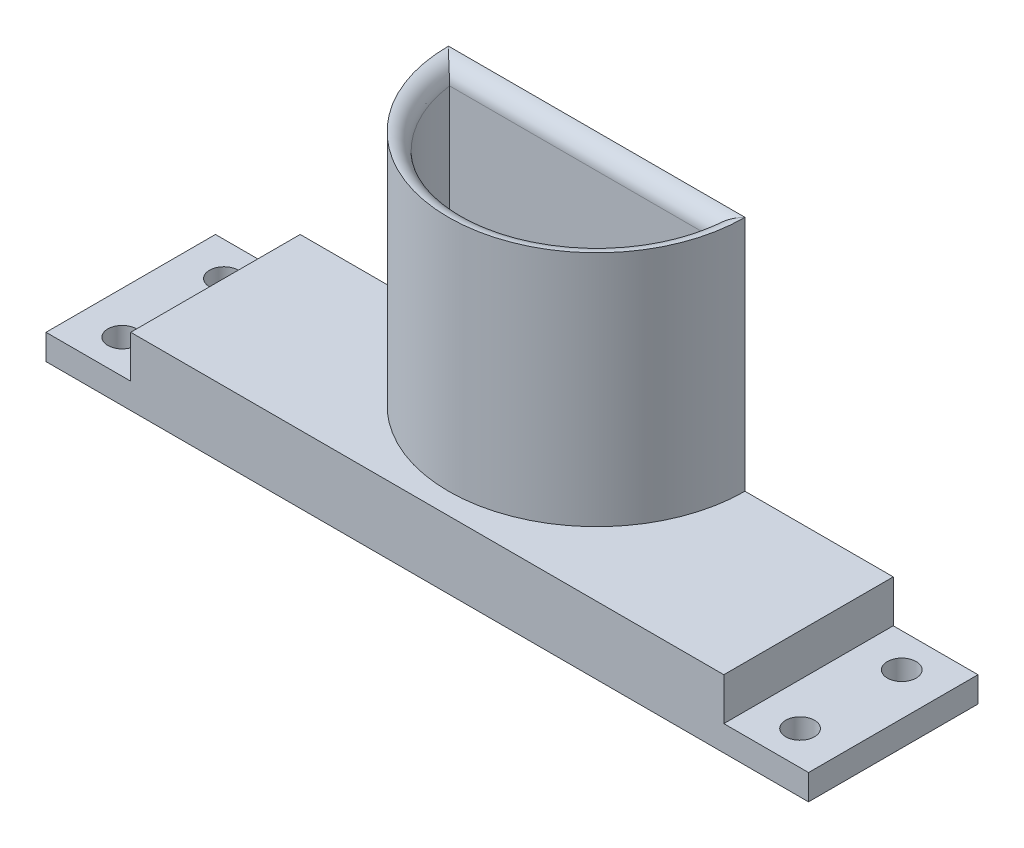
SolidWorks part; units mm, degrees
ref_plane "Front Plane" through (0, 0, 0) normal (0, 0, 1) x (1, 0, 0)
ref_plane "Top Plane" through (0, 0, 0) normal (0, 1, 0) x (1, 0, 0)
ref_plane "Right Plane" through (0, 0, 0) normal (1, 0, 0) x (0, 0, -1)
sketch "Sketch1" plane through (0, 0, 0) normal (0, 1, 0) x (1, 0, 0)
  line L1 (-35, -10) -> (35, -10)
  line L2 (-35, -10) -> (-35, 10)
  line L3 (-35, 10) -> (35, 10)
  line L4 (35, -10) -> (35, 10)
  line L5 (-35, -10) -> (35, 10) construction
  line L6 (-35, 10) -> (35, -10) construction
  point P0 (0, 0)
  dimension "D1" = 70
  dimension "D2" = 20
extrude "Boss-Extrude1" add sketch "Sketch1" along normal blind 5
sketch "Sketch2" plane through (0, 0, 0) normal (0, -1, 0) x (1, 0, 0)
  line L0 (-35, 10) -> (35, 10) construction
  line L1 (-45, -10) -> (45, -10)
  line L2 (-45, -10) -> (-45, 10)
  line L3 (-45, 10) -> (45, 10)
  line L4 (45, -10) -> (45, 10)
  line L5 (-45, -10) -> (45, 10) construction
  line L6 (-45, 10) -> (45, -10) construction
  point P0 (0, 0)
  dimension "D1" = 90
extrude "Boss-Extrude2" add sketch "Sketch2" along normal blind 3
sketch "Sketch3" plane through (0, 0, 0) normal (0, 1, 0) x (1, 0, 0)
  line L1 (-40.5, -15.25) -> (40.5, -15.25)
  line L2 (-40.5, -15.25) -> (-40.5, 15.25)
  line L3 (-40.5, 15.25) -> (40.5, 15.25)
  line L4 (40.5, -15.25) -> (40.5, 15.25)
  line L5 (-40.5, -15.25) -> (40.5, 15.25) construction
  line L6 (-40.5, 15.25) -> (40.5, -15.25) construction
  point P0 (0, 0)
  dimension "D1" = 30.5
  dimension "D2" = 81
sketch "Sketch4" plane through (0, 5, 0) normal (0, 1, 0) x (1, 0, 0)
  line L0 (35, 10) -> (-35, 10) construction
  line L1 (-17.5, 10) -> (17.5, 10)
  circle A0 centre (0, 10) radius 17.5
  line M2 (35, 10) -> (-35, 10)
  dimension "D1" = 35
extrude "Boss-Extrude3" add sketch "Sketch4" along normal blind 28 contours A0 M2 region at (0, 5, -2.5728)
sketch "Sketch6" plane through (0, 33, 0) normal (0, 1, 0) x (1, 0, 0)
  line L2 (15.3704, 8) -> (-15.3704, 8)
  line L3 (15.3704, 8) -> (-15.3704, 8)
  arc A2 (-15.3704, 8) -> (15.3704, 8) centre (0, 10) ccw
  arc A3 (-15.3704, 8) -> (15.3704, 8) centre (0, 10) ccw
  dimension "D1" = 2
extrude "Cut-Extrude1" cut sketch "Sketch6" against normal through all
fillet "Fillet1" radius 2 2 edges at (0, 33, 5.5) (0, 33, -8)
fillet "Fillet2" radius 2 2 edges at (0, -3, -8) (0, -3, 5.5)
hole_wizard "M3 Clearance Hole1" positions "Sketch7" profile "Sketch8" hole size "M3" standard "ANSI Metric"
sketch "Sketch7" plane through (0, 0, 0) normal (0, 1, 0) x (1, 0, 0)
  line L0 (-45, 10) -> (-35, 10) construction
  line L1 (35, 10) -> (45, 10) construction
  line L2 (45, -10) -> (35, -10) construction
  line L3 (-35, -10) -> (-45, -10) construction
  line L4 (-45, -10) -> (-45, 10) construction
  line L5 (45, 10) -> (45, -10) construction
  point P0 (-40, 6)
  point P2 (-40, -6)
  point P4 (40, 6)
  point P6 (40, -6)
  dimension "D1" = 4
  dimension "D2" = 4
  dimension "D3" = 4
  dimension "D4" = 4
  dimension "D5" = 5
  dimension "D6" = 5
sketch "Sketch8" plane through (-40, 0, -6) normal (1, 0, 0) x (0, 0, 1)
  line L0 (0, 0) -> (0, 11.0215)
  line L1 (0, 11.0215) -> (1.7, 10)
  line L2 (1.7, 10) -> (1.7, 0)
  line L5 (1.7, 0) -> (0, 0)
  line L10 (0, 11.0215) -> (-1.7, 10) construction
  line L11 (0, -6.35) -> (0, 107.95) construction
  dimension "Hole Dia." = 3.4
  dimension "Hole Depth" = 10
  dimension "Drill Angle" = 118
equation "\"8`\"=84.8464"
